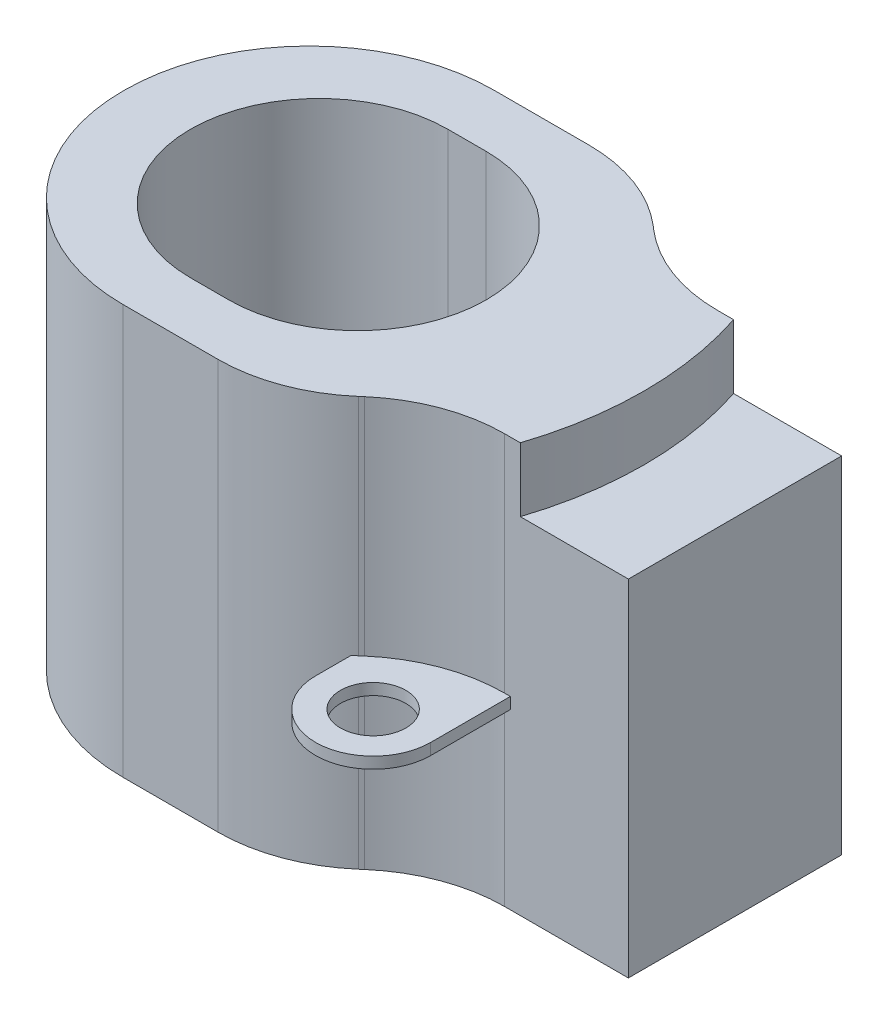
SolidWorks part; units mm, degrees
ref_plane "Front Plane" through (0, 0, 0) normal (0, 0, 1) x (1, 0, 0)
ref_plane "Top Plane" through (0, 0, 0) normal (0, 1, 0) x (1, 0, 0)
ref_plane "Right Plane" through (0, 0, 0) normal (1, 0, 0) x (0, 0, -1)
sketch "Sketch1" plane through (0, 0, 0) normal (0, 1, 0) x (1, 0, 0)
  line L0 (12.0019, -10.1775) -> (11.7764, -10.3725)
  line L1 (-2.1, 13.05) -> (4.5836, 13.05)
  line L2 (-15.1, 0.05) -> (-15.1, -0.05)
  line L3 (-2.1, -13.05) -> (4.5836, -13.05)
  line L4 (11.7764, 10.3725) -> (12.0019, 10.1775)
  line L11 (27.9, -7.5) -> (19.1948, -7.5)
  line L12 (27.9, -7.5) -> (27.9, 7.5)
  line L13 (27.9, 7.5) -> (19.1948, 7.5)
  line L15 (27.9, -7.5) -> (15.1, 7.5) construction
  line L16 (27.9, 7.5) -> (15.1, -7.5) construction
  arc A1 (-15.1, -0.05) -> (-2.1, -13.05) centre (-2.1, -0.05) ccw
  arc A2 (-2.1, 13.05) -> (-15.1, 0.05) centre (-2.1, 0.05) ccw
  arc A3 (19.1948, -7.5) -> (12.0019, -10.1775) centre (19.1948, -18.5) ccw
  arc A4 (4.5836, -13.05) -> (11.7764, -10.3725) centre (4.5836, -2.05) ccw
  arc A5 (19.1948, 7.5) -> (12.0019, 10.1775) centre (19.1948, 18.5) cw
  arc A6 (4.5836, 13.05) -> (11.7764, 10.3725) centre (4.5836, 2.05) cw
  point P0 (0, 0)
  point P2 (8.6784, 13.05)
  point P3 (-15.1, 0)
  point P4 (8.6784, -13.05)
  point P7 (21.5, 0)
  dimension "D1" = 26.1
  dimension "D5" = 13
  dimension "D4" = 11
  dimension "D2" = 15
  dimension "D3" = 43
extrude "Boss-Extrude1" add sketch "Sketch1" against normal blind 28.8
sketch "Sketch2" plane through (0, 0, 0) normal (0, 1, 0) x (1, 0, 0)
  line L0 (1.35, 0) -> (-1.35, 0) construction
  line L1 (1.35, -9.05) -> (-1.35, -9.05)
  line L2 (1.35, 9.05) -> (-1.35, 9.05)
  arc A1 (1.35, -9.05) -> (1.35, 9.05) centre (1.35, 0) ccw
  arc A2 (-1.35, 9.05) -> (-1.35, -9.05) centre (-1.35, 0) ccw
  point P3 (0, 0)
  point P9 (-10.4, 0)
  point P10 (10.4, 0)
  dimension "D1" = 18.1
  dimension "D2" = 20.8
extrude "Cut-Extrude1" cut sketch "Sketch2" against normal through all
sketch "Sketch3" plane through (0, 0, 0) normal (0, 1, 0) x (1, 0, 0)
  line L0 (19.1948, -7.5) -> (27.9, -7.5) construction
  line L1 (27.9, 7.5) -> (20.3, 7.5)
  line L2 (27.9, 7.5) -> (27.9, -7.5)
  line L3 (27.9, -7.5) -> (20.3, -7.5)
  arc A0 (20.3, 7.5) -> (20.3, -7.5) centre (-2.5375, 0) cw
  point P8 (21.5, 0)
  dimension "D2" = 1.2
  dimension "D1" = 7.6
extrude "Cut-Extrude2" cut sketch "Sketch3" against normal blind 4.5
ref_plane "Plane1" through (0, -15.8, 0) normal (0, 1, 0) x (1, 0, 0)
sketch "Sketch4" plane through (0, -15.8, 0) normal (0, 1, 0) x (1, 0, 0)
  line L0 (15.55, 13.1) -> (15.55, -13.1) construction
  line L1 (19.6, 13.1) -> (19.6, -13.1)
  line L2 (11.5, 13.1) -> (11.5, -13.1)
  line L3 (27.9, -7.5) -> (27.9, 7.5) construction
  arc A0 (19.6, 13.1) -> (11.5, 13.1) centre (15.55, 13.1) ccw
  arc A1 (11.5, -13.1) -> (19.6, -13.1) centre (15.55, -13.1) ccw
  circle A2 centre (15.55, 13.1) radius 2.3
  circle A3 centre (15.55, -13.1) radius 2.3
  point P2 (15.55, 0)
  point P9 (15.55, 17.15)
  point P10 (15.55, -17.15)
  dimension "D2" = 4.05
  dimension "D4" = 4.6
  dimension "D5" = 4.6
  dimension "D1" = 8.3
  dimension "D3" = 34.3
extrude "Boss-Extrude2" add sketch "Sketch4" against normal blind 0.8
